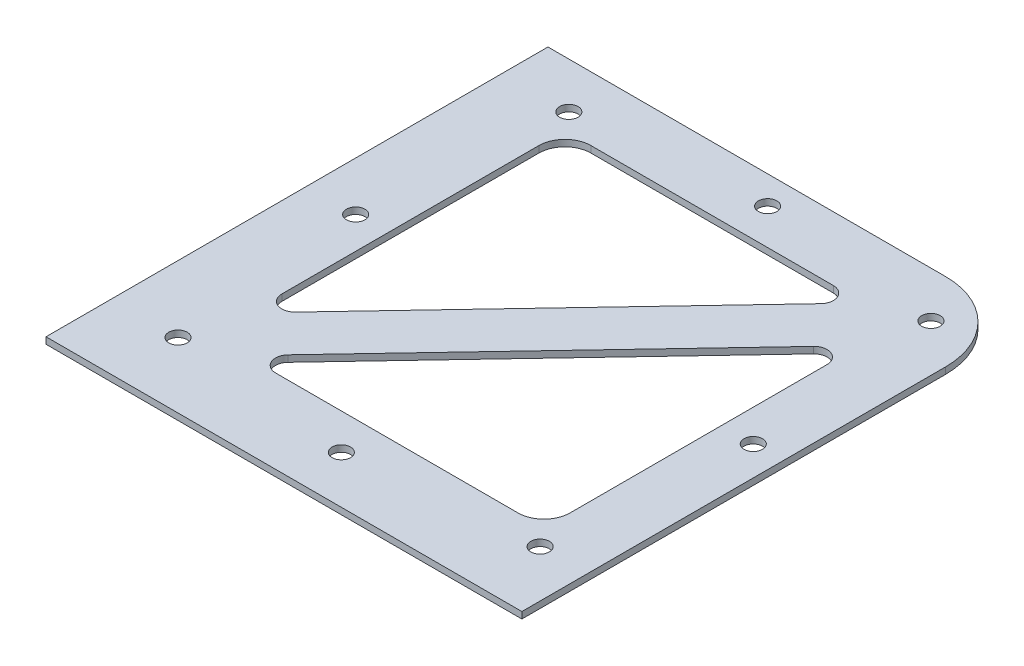
SolidWorks part; units mm, degrees
material "ASTM A36 Steel"
ref_plane "X-Y Datum" through (0, 0, 0) normal (0, 0, 1) x (1, 0, 0)
ref_plane "X-Z Datum" through (0, 0, 0) normal (0, 1, 0) x (1, 0, 0)
ref_plane "Y-Z Datum" through (0, 0, 0) normal (1, 0, 0) x (0, 0, -1)
sketch "Sketch2" plane through (0, 0, 0) normal (0, 1, 0) x (1, 0, 0)
  line L0 (-93.0565, 68.4752) -> (-93.0565, 165.4752) construction
  line L2 (-138.0565, 116.9752) -> (-48.0565, 116.9752) construction
  line L17 (-148.619, 175.7127) -> (-37.494, 175.7127)
  line L25 (-148.619, 175.7127) -> (-148.619, 58.2377)
  line L26 (-148.619, 58.2377) -> (-37.494, 58.2377)
  line L27 (-37.494, 175.7127) -> (-37.494, 58.2377)
  line L28 (-148.619, 175.7127) -> (-37.494, 58.2377) construction
  line L29 (-148.619, 58.2377) -> (-37.494, 175.7127) construction
  line L32 (-133.6965, 160.1552) -> (-52.4165, 160.1552)
  line L33 (-133.6965, 160.1552) -> (-133.6965, 73.7952)
  line L34 (-133.6965, 73.7952) -> (-52.4165, 73.7952)
  line L35 (-52.4165, 160.1552) -> (-52.4165, 73.7952)
  line L36 (-133.6965, 160.1552) -> (-52.4165, 73.7952) construction
  line L37 (-133.6965, 73.7952) -> (-52.4165, 160.1552) construction
  line L41 (-148.619, 175.7127) -> (-153.3815, 175.7127)
  line L42 (-148.619, 175.7127) -> (-148.619, 58.2377)
  line L43 (-148.619, 58.2377) -> (-153.3815, 58.2377)
  line L44 (-153.3815, 175.7127) -> (-153.3815, 58.2377)
  line L45 (-125.1615, 73.7952) -> (-52.4165, 150.6971)
  line L46 (-153.3815, 58.2377) -> (-37.494, 58.2377)
  line L47 (-153.3815, 58.2377) -> (-153.3815, 53.4752)
  line L48 (-153.3815, 53.4752) -> (-37.494, 53.4752)
  line L49 (-37.494, 58.2377) -> (-37.494, 53.4752)
  line L50 (-133.6965, 83.2533) -> (-60.9515, 160.1552)
  line L52 (-153.2321, 62.6014) -> (-42.1071, 180.0764) construction
  line L53 (-144.0059, 53.874) -> (-32.8809, 171.349) construction
  point P2 (-93.0565, 116.9752)
  point P10 (-93.0565, 116.9752)
  dimension "D1" = 117.475
  dimension "D3" = 4.7625
  dimension "D2" = 111.125
  dimension "D6" = 6.35
  dimension "D4" = 4.7625
  dimension "D5" = 86.36
  dimension "D7" = 6.35
  dimension "D8" = 81.28
extrude "Boss-Extrude4" add sketch "Sketch2" along normal blind 1.5875 contours L27 L17 L25 L26 | L41 L44 L43 L25 | L49 L26 L43 L47 L48 | L50 L33 L34 L45 L35 L32 region at (-93.0565, 0, -174.0956) region at (-151.0002, 0, -116.9752) region at (-95.4377, 0, -55.8565) region at (-93.0565, 0, -116.9752)
hole_wizard "M4 Clearance Hole1" positions "Sketch3" profile "Sketch4" hole size "M4" standard "ANSI Metric" end condition through all
sketch "Sketch3" plane through (0, 1.5875, 0) normal (0, 1, 0) x (1, 0, 0)
  point P0 (-93.0565, 65.0655)
  point P2 (-137.1479, 69.3838)
  point P4 (-141.4662, 116.9752)
  point P6 (-137.1479, 164.5666)
  point P8 (-93.0565, 168.8849)
  point P10 (-48.9651, 164.5666)
  point P12 (-44.6468, 116.9752)
  point P14 (-48.9651, 69.3838)
sketch "Sketch4" plane through (-93.0565, 1.5875, -65.0655) normal (1, 0, 0) x (0, 0, 1)
  line L0 (0, 0) -> (0, 1.5875)
  line L1 (0, 1.5875) -> (2.25, 1.5875)
  line L2 (2.25, 1.5875) -> (2.25, 0)
  line L5 (2.25, 0) -> (0, 0)
  line L11 (0, -6.35) -> (0, 107.95) construction
  dimension "Thru Hole Dia." = 4.5
  dimension "Thru Hole Depth" = 1.5875
fillet "Fillet1" radius 19.05 1 edges at (-37.494, 0.7937, -175.7127)
fillet "Fillet2" radius 6.35 2 edges at (-52.4165, 0.7937, -73.7952) (-133.6965, 0.7937, -160.1552)
fillet "Fillet3" radius 3.175 4 edges at (-52.4165, 0.7937, -150.6971) (-125.1615, 0.7937, -73.7952) (-133.6965, 0.7937, -83.2533) (-60.9515, 0.7937, -160.1552)
